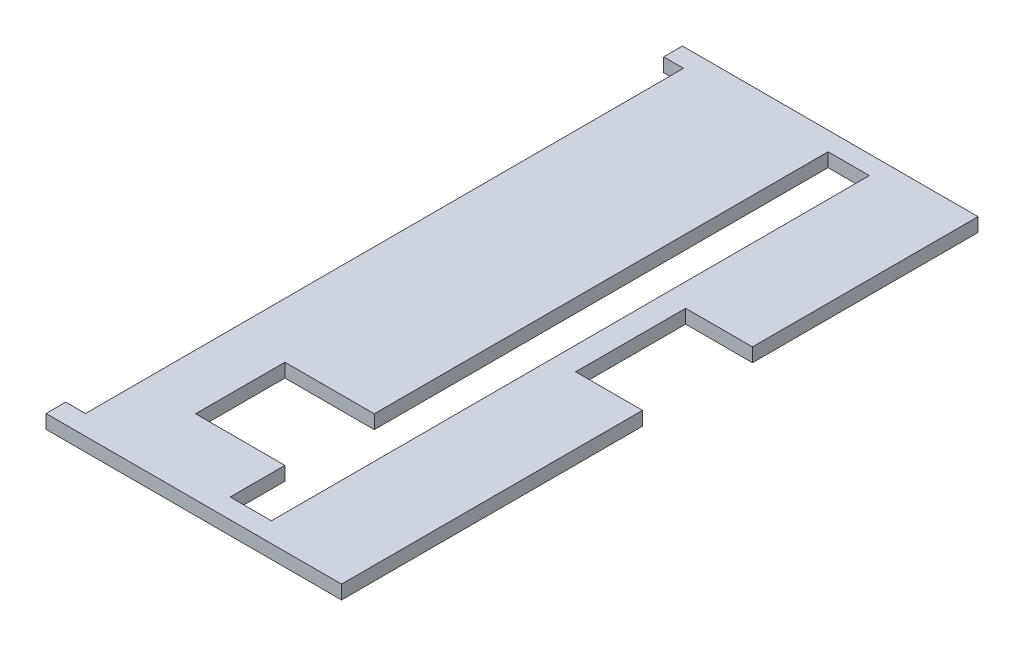
SolidWorks part; units mm, degrees
ref_plane "Front Plane" through (0, 0, 0) normal (0, 0, 1) x (1, 0, 0)
ref_plane "Top Plane" through (0, 0, 0) normal (0, 1, 0) x (1, 0, 0)
ref_plane "Right Plane" through (0, 0, 0) normal (1, 0, 0) x (0, 0, -1)
sketch "Sketch1" plane through (0, 0, 0) normal (0, 1, 0) x (1, 0, 0)
  line L1 (5911.0841, -8489.3124) -> (6341.0841, -8489.3124)
  line L2 (5911.0841, -8489.3124) -> (5911.0841, -8952.3124)
  line L3 (5911.0841, -8952.3124) -> (6341.0841, -8952.3124)
  line L4 (6341.0841, -8489.3124) -> (6341.0841, -8952.3124)
  dimension "D1" = 463
  dimension "D2" = 430
extrude "Boss-Extrude1" add sketch "Sketch1" along normal blind 10
sketch "Sketch2" plane through (0, 10, 0) normal (0, 1, 0) x (1, 0, 0)
  line L0 (5911.0841, -8489.3124) -> (5911.0841, -8952.3124) construction
  line L1 (5959.6841, -8733.0598) -> (5911.0841, -8733.0598)
  line L2 (5959.6841, -8733.0598) -> (5959.6841, -8653.0598)
  line L3 (5959.6841, -8653.0598) -> (5911.0841, -8653.0598)
  line L4 (5911.0841, -8733.0598) -> (5911.0841, -8653.0598)
  line L9 (6341.0841, -8952.3124) -> (6341.0841, -8489.3124) construction
  line L10 (6341.0841, -8733.3844) -> (6292.4841, -8733.3844)
  line L11 (6341.0841, -8733.3844) -> (6341.0841, -8653.3844)
  line L12 (6341.0841, -8653.3844) -> (6292.4841, -8653.3844)
  line L13 (6292.4841, -8733.3844) -> (6292.4841, -8653.3844)
  dimension "D1" = 48.6
  dimension "D2" = 80
  dimension "D3" = 80
  dimension "D4" = 48.6
extrude "Cut-Extrude1" cut sketch "Sketch2" against normal blind 10
sketch "Sketch3" plane through (0, 10, 0) normal (0, 1, 0) x (1, 0, 0)
  line L0 (5976.4841, -8569.3124) -> (5976.4841, -8937.9728)
  line L1 (6275.6841, -8937.9728) -> (6245.6841, -8937.9728)
  line L2 (6275.6841, -8937.9728) -> (6275.6841, -8502.9728)
  line L3 (6275.6841, -8502.9728) -> (6245.6841, -8502.9728)
  line L4 (6245.6841, -8937.9728) -> (6245.6841, -8502.9728)
  line L5 (5976.4841, -8502.9728) -> (6006.4841, -8502.9728)
  line L10 (5976.4841, -8502.9728) -> (5976.4841, -8529.3124)
  line L11 (5976.4841, -8937.9728) -> (6006.4841, -8937.9728)
  line L12 (6006.4841, -8502.9728) -> (6006.4841, -8937.9728)
  line L33 (5946.4841, -8529.3124) -> (5976.4841, -8529.3124)
  line L34 (5946.4841, -8529.3124) -> (5946.4841, -8569.3124)
  line L35 (5946.4841, -8569.3124) -> (5976.4841, -8569.3124)
  line L36 (5911.0841, -8733.0598) -> (5911.0841, -8952.3124) construction
  line L37 (6341.0841, -8952.3124) -> (6341.0841, -8733.3844) construction
  line L39 (6114.4841, -8502.9728) -> (6140.4841, -8502.9728)
  line L40 (6114.4841, -8502.9728) -> (6114.4841, -8937.9728)
  line L41 (6114.4841, -8937.9728) -> (6140.4841, -8937.9728)
  line L42 (6140.4841, -8502.9728) -> (6140.4841, -8937.9728)
  point P4 (0, 0)
  point P10 (0, 0)
  point P11 (0, 0)
  dimension "D1" = 30
  dimension "D2" = 435
  dimension "D3" = 30
  dimension "D4" = 435
  dimension "D5" = 30
  dimension "D6" = 65.4
  dimension "D7" = 40
  dimension "D8" = 65.4
  dimension "D9" = 26
  dimension "D10" = 435
  dimension "D11" = 108
extrude "Cut-Extrude2" cut sketch "Sketch3" against normal blind 10
sketch "Sketch4" plane through (0, 10, 0) normal (0, 1, 0) x (1, 0, 0)
  line L0 (6245.6841, -8502.9728) -> (6245.6841, -8937.9728) construction
  line L1 (6245.6841, -8898.0965) -> (6180.6841, -8898.0965)
  line L2 (6245.6841, -8898.0965) -> (6245.6841, -8833.0965)
  line L3 (6245.6841, -8833.0965) -> (6180.6841, -8833.0965)
  line L4 (6180.6841, -8898.0965) -> (6180.6841, -8833.0965)
  dimension "D1" = 65
  dimension "D2" = 65
extrude "Cut-Extrude3" cut sketch "Sketch4" against normal blind 10
ref_plane "Plane1" through (6126.0841, 0, 0) normal (-1, 0, 0) x (0, 0, 1)
sketch "Sketch5" plane through (6126.0841, 0, 0) normal (-1, 0, 0) x (0, 0, 1)
  line L1 (8395.6862, 142.8464) -> (9031.9061, 142.8464)
  line L2 (8395.6862, 142.8464) -> (8395.6862, -229.0644)
  line L3 (8395.6862, -229.0644) -> (9031.9061, -229.0644)
  line L4 (9031.9061, 142.8464) -> (9031.9061, -229.0644)
extrude "Cut-Extrude7" cut sketch "Sketch5" along normal blind 360
